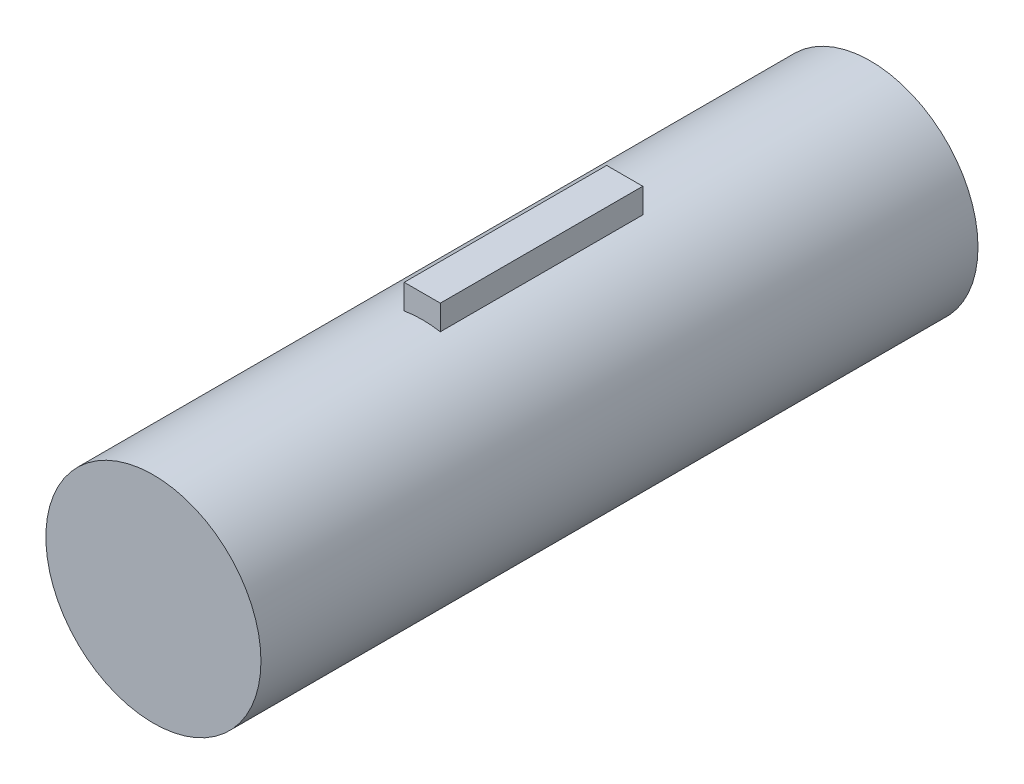
SolidWorks part; units mm, degrees
note: The reader was unsure of these and kept them because the rebuilt part matched: shared geometry of "Sketch3<2>".
ref_plane "Front Plane" through (0, 0, 0) normal (0, 0, 1) x (1, 0, 0)
ref_plane "Top Plane" through (0, 0, 0) normal (0, 1, 0) x (1, 0, 0)
ref_plane "Right Plane" through (0, 0, 0) normal (1, 0, 0) x (0, 0, -1)
sketch "Sketch1" plane through (0, 0, 0) normal (0, 0, 1) x (1, 0, 0)
  circle A0 centre (0, 0) radius 6
  dimension "D1" = 12
extrude "Boss-Extrude1" add sketch "Sketch1" against normal blind 40
ref_plane "Plane1" through (0, 6, 0) normal (0, 1, 0) x (-1, 0, 0)
sketch "Sketch3" plane through (0, 6, 0) normal (0, 1, 0) x (-1, 0, 0)
  line L0 (0, -14.9987) -> (0, -26.2927) construction
  line L1 (0, -14.9987) -> (-1.0065, -14.9987)
  line L2 (-1.0065, -14.9987) -> (-1.0065, -26.2927)
  line L3 (-1.0065, -26.2927) -> (0, -26.2927)
  line L4 (0, -26.2927) -> (1.0065, -26.2927)
  line L5 (1.0065, -26.2927) -> (1.0065, -14.9987)
  line L6 (1.0065, -14.9987) -> (0, -14.9987)
extrude "Boss-Extrude2" add sketch "Sketch3" along normal blind 1.3 separate body
extrude "Boss-Extrude3" add sketch "Sketch3<2>" against normal up to next
sketch "Sketch3<2>" plane through (0, 6, 0) normal (0, 1, 0) x (-1, 0, 0) same geometry as "Sketch3"
